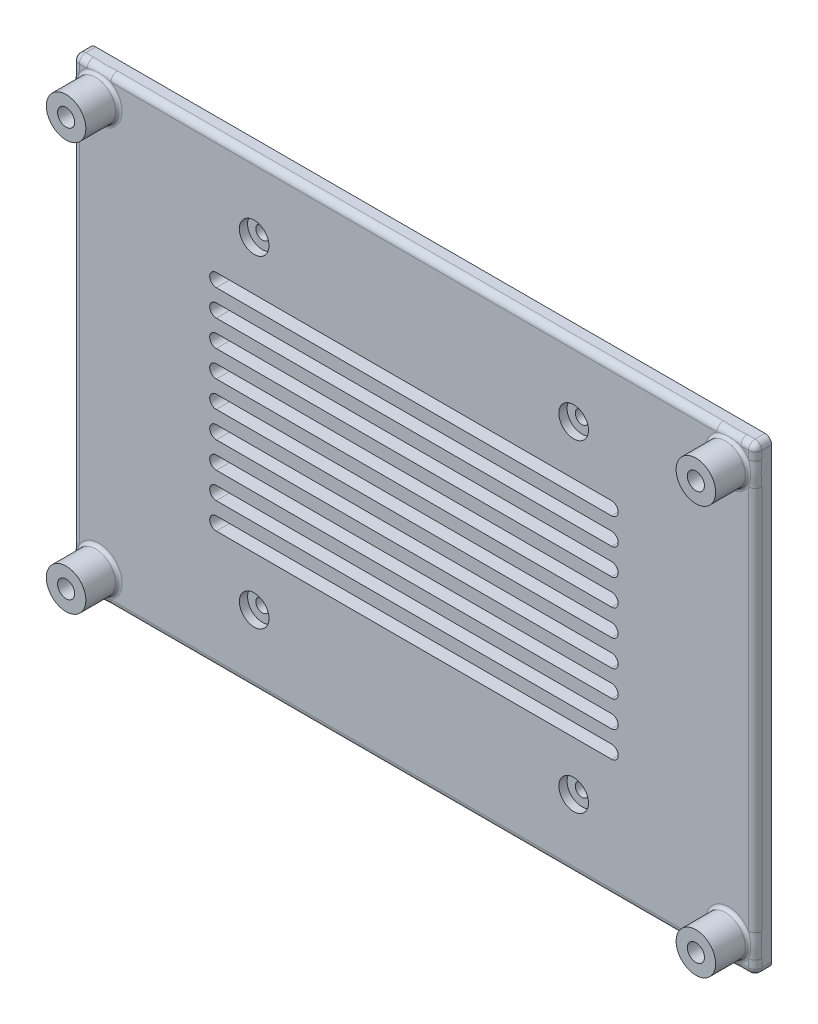
SolidWorks part; units mm, degrees
ref_plane "Plan de face" through (0, 0, 0) normal (0, 0, 1) x (1, 0, 0)
ref_plane "Plan de dessus" through (0, 0, 0) normal (0, 1, 0) x (1, 0, 0)
ref_plane "Plan de droite" through (0, 0, 0) normal (1, 0, 0) x (0, 0, -1)
sketch "Esquisse1" plane through (0, 0, 0) normal (0, 0, 1) x (1, 0, 0)
  line L1 (-51.8, 35) -> (51.8, 35)
  line L2 (-51.8, 35) -> (-51.8, -35)
  line L3 (-51.8, -35) -> (51.8, -35)
  line L4 (51.8, 35) -> (51.8, -35)
  line L5 (-51.8, 35) -> (51.8, -35) construction
  line L6 (-51.8, -35) -> (51.8, 35) construction
  line L7 (24.25, -24.5) -> (-24.25, -24.5) construction
  line L8 (24.25, -24.5) -> (24.25, 24.5) construction
  line L9 (24.25, 24.5) -> (-24.25, 24.5) construction
  line L10 (-24.25, -24.5) -> (-24.25, 24.5) construction
  line L11 (24.25, -24.5) -> (-24.25, 24.5) construction
  line L12 (24.25, 24.5) -> (-24.25, -24.5) construction
  circle A0 centre (-24.25, -24.5) radius 1.005
  circle A1 centre (-24.25, 24.5) radius 1.005
  circle A2 centre (24.25, -24.5) radius 1.005
  circle A3 centre (24.25, 24.5) radius 1.005
  point P0 (0, 0)
  point P5 (0, 0)
  point P13 (0, 0)
  dimension "D5" = 2.01
  dimension "D6" = 2.01
  dimension "D7" = 2.01
  dimension "D8" = 2.01
  dimension "D1" = 70
  dimension "D2" = 103.6
  dimension "D3" = 48.5
  dimension "D4" = 49
extrude "Boss.-Extru.1" add sketch "Esquisse1" along normal blind 2.5
sketch "Esquisse3" plane through (0, 0, 2.5) normal (0, 0, 1) x (1, 0, 0)
  line L0 (51.8, 35) -> (-51.8, 35) construction
  line L1 (-51.8, 35) -> (-51.8, -35) construction
  line L2 (-51.8, -35) -> (51.8, -35) construction
  line L3 (51.8, -35) -> (51.8, 35) construction
  circle A0 centre (-47.8, 31) radius 3
  circle A1 centre (47.8, 31) radius 3
  circle A2 centre (-47.8, -31) radius 3
  circle A3 centre (47.8, -31) radius 3
  point P17 (-47.8, 31)
  point P18 (-47.8, -31)
  point P19 (47.8, -31)
  point P20 (47.8, 31)
  dimension "D3" = 4
  dimension "D1" = 4
  dimension "D2" = 4
  dimension "D4" = 4
  dimension "D5" = 4
  dimension "D6" = 4
  dimension "D7" = 4
  dimension "D8" = 4
extrude "Boss.-Extru.2" add sketch "Esquisse3" along normal blind 5 contours A1 | A3 | A2 | A0
fillet "Congé2" radius 0.5 4 edges at (50.8, 31, 2.5) (50.8, -31, 2.5) (-44.8, -31, 2.5) (-44.8, 31, 2.5)
hole_wizard "Trou pour taraudage pour trou taraudé M32" positions "Esquisse15" profile "Esquisse16" hole size "M3" standard "AS"
sketch "Esquisse15" plane through (0, 0, 7.5) normal (0, 0, 1) x (1, 0, 0)
  point P0 (-47.8, -31)
  point P3 (47.8, -31)
  point P6 (47.8, 31)
  point P9 (-47.8, 31)
sketch "Esquisse16" plane through (-47.8, -31, 7.5) normal (1, 0, 0) x (0, -1, 0)
  line L0 (0, 0) -> (0, 5.7811)
  line L1 (0, 5.7811) -> (1.3, 5)
  line L2 (1.3, 5) -> (1.3, 0)
  line L5 (1.3, 0) -> (0, 0)
  line L10 (0, 5.7811) -> (-1.3, 5) construction
  line L11 (0, -6.35) -> (0, 107.95) construction
  dimension "Diamètre du perçage" = 2.6
  dimension "Profondeur du perçage" = 5
  dimension "Angle de pointe" = 118
sketch "Esquisse19" plane through (0, 0, 2.5) normal (0, 0, 1) x (1, 0, 0)
  circle A0 centre (24.25, -24.5) radius 2.25
  circle A1 centre (-24.25, -24.5) radius 2.25
  circle A2 centre (-24.25, 24.5) radius 2.25
  circle A3 centre (24.25, 24.5) radius 2.25
extrude "Enlèv. mat.-Extru.1" cut sketch "Esquisse19" against normal blind 1.25 contours A1 | A2 | A3 | A0
fillet "Congé3" radius 1 8 edges at (-51.8, 0, 2.5) (0, -35, 2.5) (0, 35, 2.5) (51.8, 0, 2.5) (51.8, -35, 1.25) (51.8, 35, 1.25) (-51.8, 35, 1.25) (-51.8, -35, 1.25)
sketch "Esquisse22" plane through (0, 0, 2.5) normal (0, 0, 1) x (1, 0, 0)
  line L0 (30, 0) -> (-30, 0) construction
  line L1 (30, -1) -> (-30, -1)
  line L2 (30, 1) -> (-30, 1)
  arc A0 (30, -1) -> (30, 1) centre (30, 0) ccw
  arc A1 (-30, 1) -> (-30, -1) centre (-30, 0) ccw
  point P2 (0, 0)
extrude "Enlèv. mat.-Extru.3" cut sketch "Esquisse22" against normal through all
pattern_linear "Répétition linéaire2" count 5 spacing 4 along (0, 1, 0) count 5 spacing 4 along (0, -1, 0) of "Enlèv. mat.-Extru.3" pattern seed only yes
